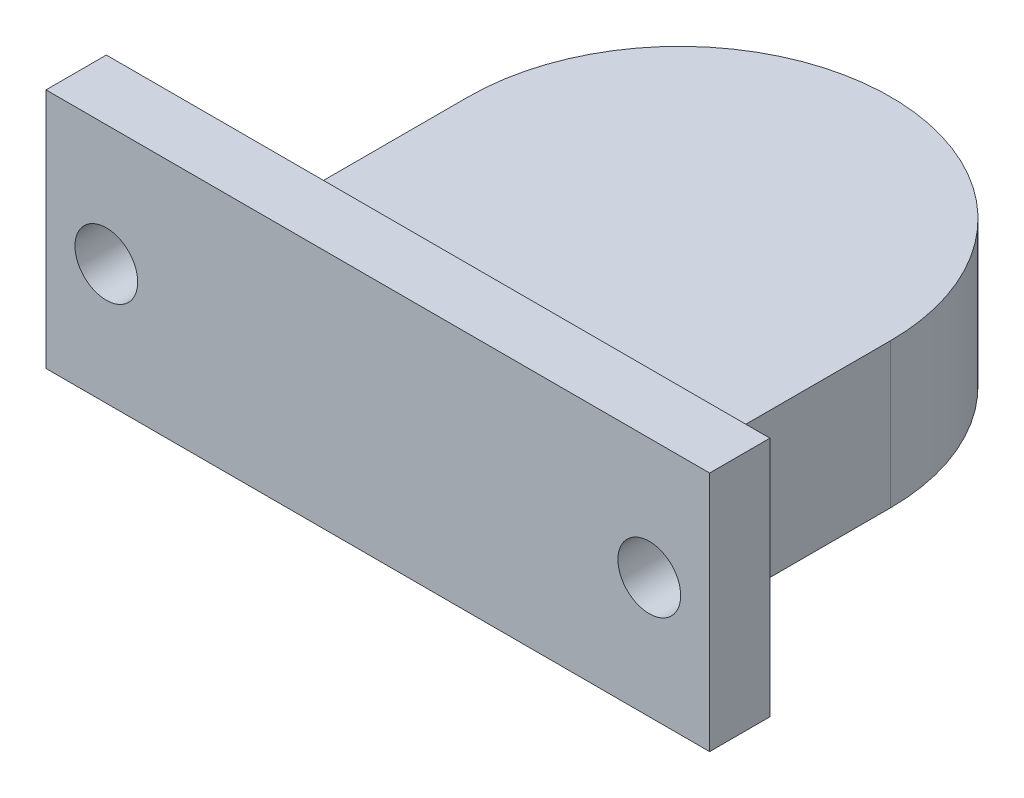
SolidWorks part; units mm, degrees
material "PET"
ref_plane "Front Plane" through (0, 0, 0) normal (0, 0, 1) x (1, 0, 0)
ref_plane "Top Plane" through (0, 0, 0) normal (0, 1, 0) x (1, 0, 0)
ref_plane "Right Plane" through (0, 0, 0) normal (1, 0, 0) x (0, 0, -1)
sketch "Sketch1" plane through (0, 0, 0) normal (0, 1, 0) x (1, 0, 0)
  line L5 (-17.5, 0) -> (-17.5, -20)
  line L6 (17.5, 0) -> (17.5, -20)
  line L9 (-17.5, -20) -> (17.5, -20)
  circle A0 centre (0, 0) radius 11.1
  arc A1 (17.5, 0) -> (-17.5, 0) centre (0, 0) ccw
  dimension "D1" = 22.2
  dimension "D2" = 35
  dimension "D3" = 20
extrude "Boss-Extrude1" add sketch "Sketch1" along normal blind 12
sketch "Sketch3" plane through (0, 12, 0) normal (0, 1, 0) x (1, 0, 0)
  circle A0 centre (0, 0) radius 11.1
  circle A1 centre (0, 0) radius 11.1 construction
extrude "Boss-Extrude2" add sketch "Sketch3" against normal blind 2
sketch "Sketch4" plane through (0, 0, 0) normal (0, 1, 0) x (1, 0, 0)
  line L0 (-17.5, -20) -> (17.5, -20) construction
  line L1 (-27.5, -20) -> (27.5, -20)
  line L2 (-27.5, -20) -> (-27.5, -25)
  line L3 (-27.5, -25) -> (27.5, -25)
  line L4 (27.5, -20) -> (27.5, -25)
  point P6 (0, -20)
  dimension "D1" = 5
  dimension "D2" = 55
extrude "Boss-Extrude3" add sketch "Sketch4" along normal blind 20
sketch "Sketch5" plane through (0, 0, 20) normal (0, 0, -1) x (-1, 0, 0)
  line L0 (-27.5, 10) -> (27.5, 10) construction
  line L1 (-27.5, 20) -> (-27.5, 0) construction
  line L2 (27.5, 20) -> (27.5, 0) construction
  line L3 (-17.5, 12) -> (-17.5, 0) construction
  line L4 (17.5, 12) -> (17.5, 0) construction
  circle A0 centre (22.5, 10) radius 2.6
  circle A1 centre (-22.5, 10) radius 2.6
  dimension "D1" = 5.2
  dimension "D2" = 5.2
  dimension "D3" = 5
  dimension "D4" = 5
  dimension "D5" = 5
  dimension "D6" = 5
extrude "Cut-Extrude1" cut sketch "Sketch5" against normal through all
chamfer "Chamfer1" distance 8 angle 45 1 edges at (0, 12, 20)
equation "\"tolerance\"= 0.2"
equation "\"D1@Sketch1\"=\"tolerance\"+22"
